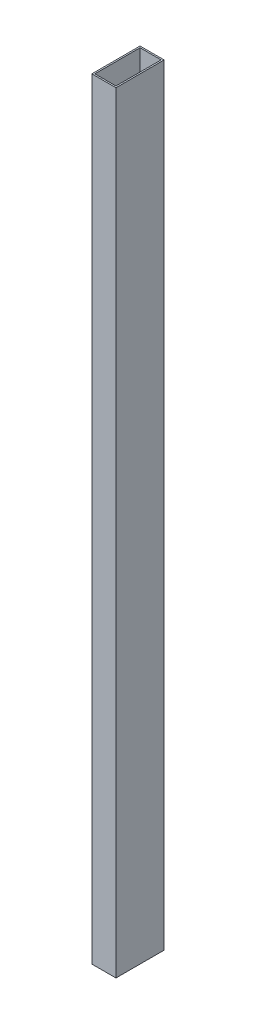
SolidWorks part; units mm, degrees
material "6061-T6 (SS)"
ref_plane "Front" through (0, 0, 0) normal (0, 0, 1) x (1, 0, 0)
ref_plane "Top" through (0, 0, 0) normal (0, 1, 0) x (1, 0, 0)
ref_plane "Right" through (0, 0, 0) normal (1, 0, 0) x (0, 0, -1)
sketch "Sketch1" plane through (0, 0, 0) normal (0, 1, 0) x (1, 0, 0)
  line L1 (12.7, 25.4) -> (-12.7, 25.4)
  line L2 (12.7, 25.4) -> (12.7, -25.4)
  line L3 (12.7, -25.4) -> (-12.7, -25.4)
  line L4 (-12.7, 25.4) -> (-12.7, -25.4)
  line L5 (12.7, 25.4) -> (-12.7, -25.4) construction
  line L6 (12.7, -25.4) -> (-12.7, 25.4) construction
  point P0 (0, 0)
  dimension "D1" = 25.4
  dimension "D2" = 50.8
extrude "Extrude-Thin1" add sketch "Sketch1" along normal blind 812.8 thin thin type one direction reverse wall 1.5875
